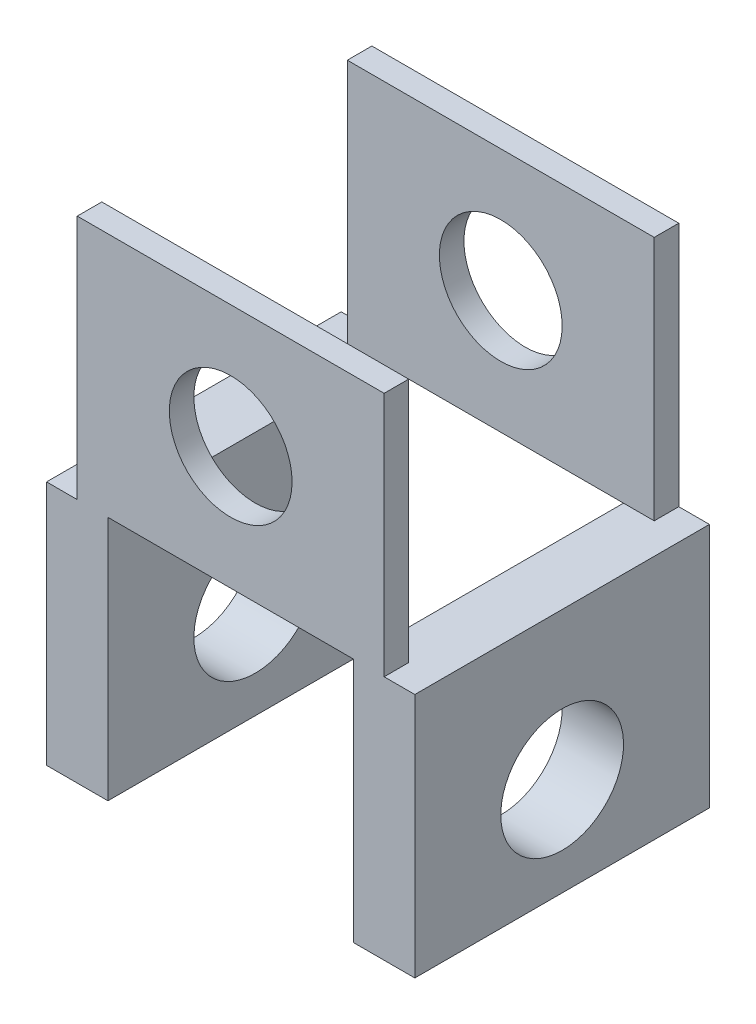
SolidWorks part; units mm, degrees
note: The reader was unsure of these and kept them because the rebuilt part matched: shared geometry of "Sketch1<3>".
ref_plane "Front Plane" through (0, 0, 0) normal (0, 0, 1) x (1, 0, 0)
ref_plane "Top Plane" through (0, 0, 0) normal (0, 1, 0) x (1, 0, 0)
ref_plane "Right Plane" through (0, 0, 0) normal (1, 0, 0) x (0, 0, -1)
sketch "Sketch1" plane through (0, 0, 0) normal (0, 0, 1) x (1, 0, 0)
  line L0 (10, -30) -> (15, -30)
  line L1 (-12.5, -10) -> (12.5, -10)
  line L2 (-12.5, -10) -> (-12.5, 10)
  line L3 (-12.5, 10) -> (12.5, 10)
  line L4 (12.5, -10) -> (12.5, 10)
  line L5 (-12.5, -10) -> (12.5, 10) construction
  line L6 (-12.5, 10) -> (12.5, -10) construction
  line L7 (-15, -10) -> (15, -10)
  line L8 (-15, -10) -> (-15, -30)
  line L9 (-15, -30) -> (-10, -30)
  line L10 (15, -10) -> (15, -30)
  line L11 (-10, -10) -> (10, -10)
  line L12 (-10, -10) -> (-10, -30)
  line L14 (10, -10) -> (10, -30)
  circle A0 centre (0, 0) radius 5
  point P0 (0, 0)
  point P16 (0, 0)
  point P17 (0, 0)
  dimension "D3" = 10
  dimension "D1" = 25
  dimension "D2" = 20
  dimension "D4" = 5
  dimension "D5" = 2.5
  dimension "D6" = 2.5
  dimension "D7" = 5
  dimension "D8" = 20
extrude "Boss-Extrude1" add sketch "Sketch1" along normal blind 2 contours L1 L7 L4 L3 L2 A0
extrude "Boss-Extrude2" add sketch "Sketch1<3>" along normal blind 12 contours L1 L14 L0 L10 L7 | L12 L1 L7 L8 L9
sketch "Sketch1<3>" plane through (0, 0, 0) normal (0, 0, 1) x (1, 0, 0) same geometry as "Sketch1"
ref_plane "Plane1" through (0, 0, 12) normal (0, 0, 1) x (1, 0, 0)
mirror "Mirror1" about plane through (0, 0, 12) normal (0, 0, 1) of "Boss-Extrude2", "Boss-Extrude1"
mirror "Mirror2" about plane through (0, 0, 12) normal (0, 0, 1) of "Boss-Extrude1"
sketch "Sketch2" plane through (-15, 0, 0) normal (-1, 0, 0) x (0, 0, 1)
  line L0 (12, -10) -> (12, -30) construction
  line L1 (24, -10) -> (0, -10) construction
  line L2 (24, -30) -> (0, -30) construction
  circle A0 centre (12, -22) radius 5
  dimension "D1" = 10
  dimension "D2" = 8
extrude "Cut-Extrude1" cut sketch "Sketch2" against normal blind 48
